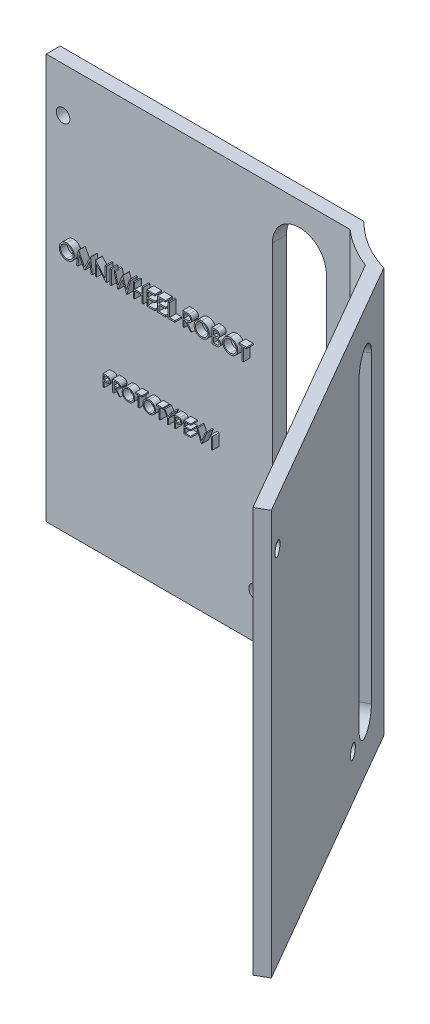
SolidWorks part; units mm, degrees
ref_plane "Plan de face" through (0, 0, 0) normal (0, 0, 1) x (1, 0, 0)
ref_plane "Plan de dessus" through (0, 0, 0) normal (0, 1, 0) x (1, 0, 0)
ref_plane "Plan de droite" through (0, 0, 0) normal (1, 0, 0) x (0, 0, -1)
sketch "Esquisse3" plane through (0, 0, 0) normal (0, 1, 0) x (1, 0, 0)
  line L0 (-150.1573, 0) -> (189.6273, 0) construction
  line L1 (-83.8395, -145.9242) -> (87.7229, 151.2306) construction
  line L2 (-78.0725, 135.2255) -> (117.7517, -203.9519) construction
  line L3 (-125, 131.2995) -> (-125, -153.5705) construction
  line L4 (-25, -24.4949) -> (-115, -24.4949)
  line L6 (-21.2883, 25.5051) -> (-23.9685, 25.5051)
  line L7 (-115, -24.4949) -> (-115, 25.5051)
  line L8 (-25, -24.4949) -> (-115, 25.5051) construction
  line L9 (-21.2883, 25.5051) -> (-115, -24.4949) construction
  line L10 (-23.9685, 25.5051) -> (-115, 25.5051)
  line L11 (34.0723, 8.0048) -> (79.5881, 86.8404)
  line L12 (36.2868, 111.8404) -> (79.5881, 86.8404)
  line L13 (-8.7132, 33.8981) -> (36.2868, 111.8404)
  line L14 (-10.1038, -33.5099) -> (35.4119, -112.3455)
  line L15 (78.7132, -87.3455) -> (35.4119, -112.3455)
  line L16 (33.7132, -9.4032) -> (78.7132, -87.3455)
  line L17 (-23.9685, 25.5051) -> (-25, -24.4949)
  line L18 (-8.7132, 33.8981) -> (34.0723, 8.0048)
  line L19 (-10.1038, -33.5099) -> (33.7132, -9.4032)
  line L20 (-25, -28.6182) -> (-115, -28.6182)
  line L21 (-115, -28.6182) -> (-115, -24.4949)
  line L22 (-13.5526, -35.5011) -> (31.9631, -114.3367)
  line L23 (31.9631, -114.3367) -> (35.4119, -112.3455)
  circle A0 centre (0, 0) radius 125
  circle A1 centre (0, 0) radius 35
  circle A2 centre (0, 0) radius 125
  circle A3 centre (0, 0) radius 125
  circle A4 centre (0, 0) radius 38
  point P9 (-69.0908, 0)
  point P32 (0, 0)
  dimension "D1" = 250
  dimension "D4" = 70
  dimension "D2" = 120
  dimension "D3" = 120
  dimension "D5" = 10
  dimension "D6" = 50
  dimension "D7" = 90
  dimension "D9" = 3
  dimension "D8" = 3
extrude "Boss.-Extru.1" add sketch "Esquisse3" along normal blind 120 contours A4 L4 L21 L20 | L4 A4 L14 A1 | A4 L22 L23 L14 region at (-18.6168, 0, 30.8794) region at (-71.0566, 0, 26.5723) region at (11.4638, 0, 74.8797)
sketch "Esquisse4" plane through (0, 0, 28.6182) normal (0, 0, 1) x (1, 0, 0)
  line L0 (-40, 120) -> (-40, 0) construction
  line L1 (-25, 120) -> (-115, 120) construction
  line L2 (-25, 0) -> (-115, 0) construction
  line L3 (-48, 105) -> (-48, 15)
  line L4 (-25, 120) -> (-25, 0) construction
  line L5 (-115, 60) -> (-20.315, 60) construction
  line L6 (-115, 120) -> (-115, 0) construction
  line L7 (-32, 105) -> (-32, 15)
  arc A0 (-48, 15) -> (-32, 15) centre (-40, 15) ccw
  arc A1 (-48, 105) -> (-32, 105) centre (-40, 105) cw
  dimension "D1" = 8
  dimension "D2" = 15
  dimension "D3" = 45
  dimension "D4" = 45
extrude "Enlèv. mat.-Extru.1" cut sketch "Esquisse4" against normal through all
sketch "Esquisse5" plane through (-25.5369, 0, 14.7437) normal (-0.866, 0, 0.5) x (0.5, 0, 0.866)
  line L0 (38.9685, 120) -> (38.9685, 0) construction
  line L1 (23.9685, 120) -> (115, 120) construction
  line L2 (43.9685, 105) -> (43.9685, 15)
  line L3 (38.9685, 60) -> (127.8483, 60) construction
  line L4 (115, 120) -> (115, 0) construction
  line L5 (23.9685, 120) -> (23.9685, 0) construction
  line L6 (33.9685, 105) -> (33.9685, 15)
  arc A0 (43.9685, 15) -> (33.9685, 15) centre (38.9685, 15) cw
  arc A1 (43.9685, 105) -> (33.9685, 105) centre (38.9685, 105) ccw
  point P14 (115, 60)
  dimension "D1" = 5
  dimension "D2" = 45
  dimension "D3" = 45
  dimension "D4" = 15
extrude "Enlèv. mat.-Extru.2" cut sketch "Esquisse5" against normal through all
sketch "Esquisse6" plane through (0, 0, 28.6182) normal (0, 0, 1) x (1, 0, 0)
  circle A0 centre (-110, 106.75) radius 2 construction
  circle A1 centre (-110, 106.75) radius 2
sketch "Esquisse7" plane through (-25.5369, 0, 14.7437) normal (-0.866, 0, 0.5) x (0.5, 0, 0.866)
  circle A0 centre (110, 106.75) radius 2 construction
  circle A1 centre (110, 106.75) radius 2
extrude "Enlèv. mat.-Extru.3" cut sketch "Esquisse6" against normal through all
extrude "Enlèv. mat.-Extru.4" cut sketch "Esquisse7" against normal through all
sketch "Esquisse8" plane through (0, 0, 28.6182) normal (0, 0, 1) x (1, 0, 0)
  line L0 (-115, 72.2203) -> (-48, 72.2203) construction
  line L1 (-107.7615, 44.975) -> (-51.4576, 44.975) construction
  line L2 (-115, 120) -> (-115, 0) construction
  line L3 (-48, 105) -> (-48, 15) construction
  text T0 "OMNIWHEEL ROBOT" font "Century Gothic" height in points 16
  text T1 "PROTOTYPE V1" font "Century Gothic" height 3.5
extrude "Boss.-Extru.2" add sketch "Esquisse8" along normal blind 2
sketch "Esquisse9" plane through (0, 0, 28.6182) normal (0, 0, 1) x (1, 0, 0)
  circle A0 centre (-53, 13) radius 2 construction
  circle A1 centre (-53, 13) radius 2
sketch "Esquisse10" plane through (-25.5369, 0, 14.7437) normal (-0.866, 0, 0.5) x (0.5, 0, 0.866)
  circle A0 centre (48.9685, 13) radius 2 construction
  circle A1 centre (48.9685, 13) radius 2
extrude "Enlèv. mat.-Extru.5" cut sketch "Esquisse9" against normal through all
extrude "Enlèv. mat.-Extru.6" cut sketch "Esquisse10" against normal through all
